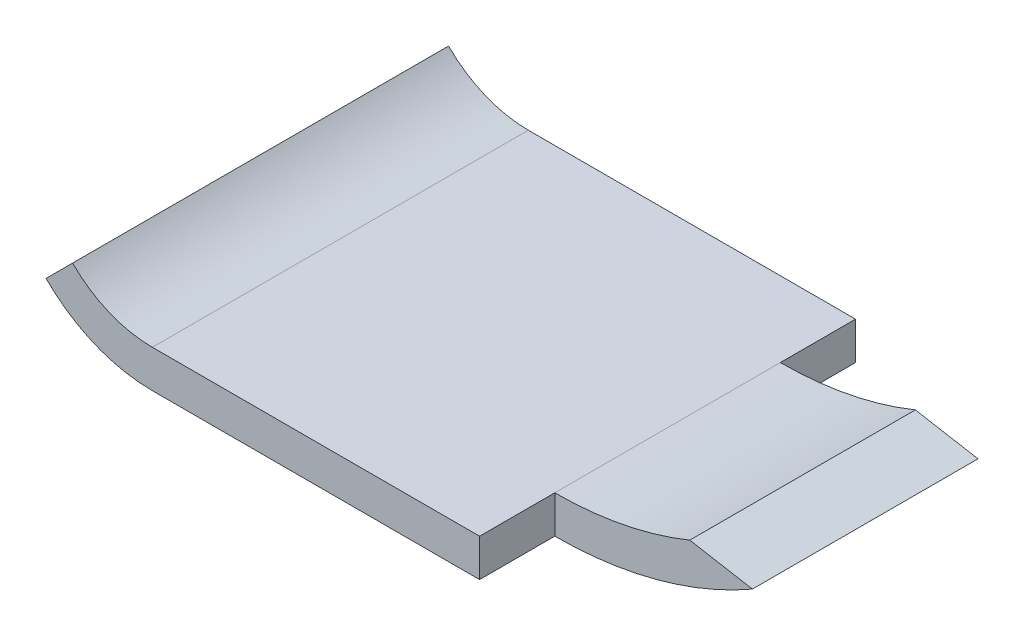
SolidWorks part; units mm, degrees
note: The reader was unsure of these and kept them because the rebuilt part matched: shared geometry of "Sketch2<2>".
ref_plane "Front Plane" through (0, 0, 0) normal (0, 0, 1) x (1, 0, 0)
ref_plane "Top Plane" through (0, 0, 0) normal (0, 1, 0) x (1, 0, 0)
ref_plane "Right Plane" through (0, 0, 0) normal (1, 0, 0) x (0, 0, -1)
sketch "Sketch1" plane through (0, 0, 0) normal (0, 0, 1) x (1, 0, 0)
  line L0 (-6.9088, 0) -> (6.9088, 0)
  line L1 (-11.3989, 1.8599) -> (-10.2764, 2.9824)
  line L2 (15.2545, 2.2398) -> (12.609, 2.7062)
  line L3 (-6.9088, 1.5875) -> (6.9088, 1.5875)
  arc A0 (-6.9088, 0) -> (-11.3989, 1.8599) centre (-6.9088, 6.35) cw
  arc A1 (6.9088, 0) -> (15.2545, 2.2398) centre (6.9088, 16.6687) ccw
  arc A2 (-10.2764, 2.9824) -> (-6.9088, 1.5875) centre (-6.9088, 6.35) ccw
  arc A3 (6.9088, 1.5875) -> (12.609, 2.7062) centre (6.9088, 16.6687) ccw
  point P4 (0, 0)
  dimension "D3" = 6.35
  dimension "D4" = 16.6687
  dimension "D1" = 13.8176
  dimension "D2" = 45
  dimension "D5" = 10
  dimension "D6" = 1.5875
  dimension "D7" = 22.8854
extrude "Boss-Extrude1" add sketch "Sketch1" along normal blind 9.525
sketch "Sketch2" plane through (0, 0, 9.525) normal (0, 0, 1) x (1, 0, 0)
  line L0 (6.9088, 0) -> (6.9088, 1.5875)
  line L4 (15.2545, 2.2398) -> (12.609, 2.7062)
  line L5 (6.9088, 1.5875) -> (-6.9088, 1.5875)
  line L6 (-10.2764, 2.9824) -> (-11.3989, 1.8599)
  line L7 (-6.9088, 0) -> (6.9088, 0)
  line L9 (6.9088, 1.5875) -> (-6.9088, 1.5875)
  line L10 (-10.2764, 2.9824) -> (-11.3989, 1.8599)
  line L11 (-6.9088, 0) -> (6.9088, 0)
  arc A4 (6.9088, 0) -> (15.2545, 2.2398) centre (6.9088, 16.6687) ccw
  arc A5 (6.9088, 1.5875) -> (12.609, 2.7062) centre (6.9088, 16.6687) ccw
  arc A6 (-10.2764, 2.9824) -> (-6.9088, 1.5875) centre (-6.9088, 6.35) ccw
  arc A7 (-11.3989, 1.8599) -> (-6.9088, 0) centre (-6.9088, 6.35) ccw
  arc A10 (-10.2764, 2.9824) -> (-6.9088, 1.5875) centre (-6.9088, 6.35) ccw
  arc A11 (-11.3989, 1.8599) -> (-6.9088, 0) centre (-6.9088, 6.35) ccw
  dimension "D1" = 0
extrude "Boss-Extrude2" add sketch "Sketch2" along normal blind 3.175
extrude "Boss-Extrude3" add sketch "Sketch2<2>" against normal blind 3.175 from surface at -9.525
sketch "Sketch2<2>" plane through (0, 0, 9.525) normal (0, 0, 1) x (1, 0, 0) same geometry as "Sketch2"
ref_plane "Plane1" through (0, 0, 4.7625) normal (0, 0, -1) x (-1, 0, 0)
sketch "Sketch3" plane through (0, 0, 4.7625) normal (0, 0, -1) x (-1, 0, 0)
  line L0 (6.9088, 0) -> (11.3989, 1.8599) construction
  arc A0 (6.9088, 0) -> (11.3989, 1.8599) centre (6.9088, 6.35) ccw construction
  arc A1 (6.9088, 0) -> (11.3989, 1.8599) centre (6.9088, 6.35) ccw
  arc A2 (6.9088, 0) -> (16.8066, 0.6632) centre (11.3276, 8.2426) ccw
  arc A3 (11.3989, 1.8599) -> (16.8066, 0.6632) centre (15.3965, 7.108) ccw
  point P6 (14.931, -3.5456)
  point P7 (15.0485, 0)
  point P8 (13.4813, -0.7142)
  point P9 (14.9199, 0)
  point P10 (12.9172, -0.9478)
  point P11 (14.1817, -0.424)
  point P12 (16.8066, 0.6632)
  dimension "D1" = 3.175
